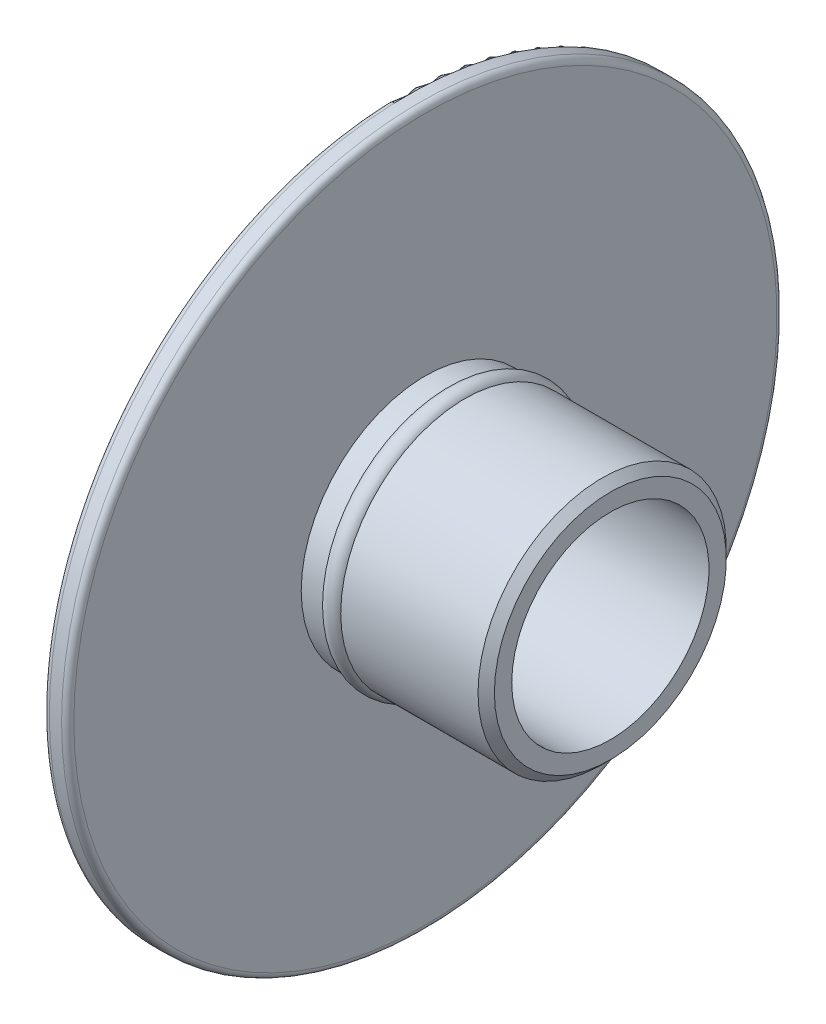
SolidWorks part; units mm, degrees
material "3D Printed PLA"
ref_plane "Front Plane" through (0, 0, 0) normal (0, 0, 1) x (1, 0, 0)
ref_plane "Top Plane" through (0, 0, 0) normal (0, 1, 0) x (1, 0, 0)
ref_plane "Right Plane" through (0, 0, 0) normal (1, 0, 0) x (0, 0, -1)
ref_axis "Axis1" through (0, 55, 0) along (0, -1, 0)
ref_axis "Axis2" through (-88.99, 0, 0) along (1, 0, 0)
ref_axis "Axis3" through (0, 0, -88.99) along (0, 0, 1)
sketch "Sketch1" plane through (0, 0, 0) normal (0, 0, 1) x (1, 0, 0)
  line L0 (0, 0) -> (0, 6029.5309) construction
  line L1 (0, 0) -> (6029.5309, 0) construction
  line L2 (-5.25, 16) -> (-5.25, 17.5)
  line L3 (-5.25, 16) -> (5.25, 16)
  line L4 (-5.25, 16) -> (-5.25, -16)
  line L5 (-5.25, -16) -> (5.25, -16)
  line L6 (5.25, 16) -> (5.25, -16)
  line L7 (-5.25, 17.5) -> (-6.45, 17.5)
  line L8 (-6.45, 17.5) -> (-6.45, -17.5)
  line L9 (-6.45, -17.5) -> (-5.25, -17.5)
  line L10 (-5.25, -17.5) -> (-5.25, -16)
  line L11 (5.25, -17.5) -> (5.25, -16)
  line L12 (6.45, -17.5) -> (5.25, -17.5)
  line L13 (6.45, 17.5) -> (6.45, -17.5)
  line L14 (5.25, 17.5) -> (6.45, 17.5)
  line L15 (5.25, 16) -> (5.25, 17.5)
  line L16 (-6.45, 4.8246) -> (6.45, 4.8246)
  line L17 (-5.05, 7.5246) -> (-5.05, 6.2746)
  line L18 (-5.25, 6.0746) -> (-4.183, 6.0746)
  line L19 (3.8, 6.0746) -> (3.8, 4.8246)
  line L20 (4, 4.8246) -> (4, 6.2746)
  line L21 (4, 6.2746) -> (-3.3929, 6.2746)
  line L22 (-4.1071, 6.2746) -> (-5.05, 6.2746)
  line L23 (-3.3929, 6.2746) -> (-4.1071, 6.2746) construction
  line L24 (-4.183, 6.0746) -> (-3.317, 6.0746) construction
  line L25 (-3.317, 6.0746) -> (3.8, 6.0746)
  line L26 (-5.05, 7.5246) -> (5.25, 7.5246)
  line L27 (-3.75, 5.9246) -> (-3.75, 5.8246) construction
  line L28 (3.8, 6.0746) -> (3.8, 6.2746) construction
  line L29 (3.8, 6.0746) -> (4, 6.0746) construction
  line L30 (-4, -4.8246) -> (-4, -6.2746)
  line L31 (-3.75, 6.3246) -> (-3.75, 6.4246) construction
  line L32 (4, 6.2746) -> (5.25, 6.2746) construction
  line L33 (-5.05, 7.5246) -> (-5.25, 7.5246) construction
  line L34 (-4, -6.2746) -> (3.3929, -6.2746)
  line L35 (4.1071, -6.2746) -> (5.05, -6.2746)
  line L36 (5.05, -7.5246) -> (5.05, -6.2746)
  line L37 (5.05, -7.5246) -> (-5.25, -7.5246)
  line L38 (5.25, -6.0746) -> (4.183, -6.0746)
  line L39 (3.317, -6.0746) -> (-3.8, -6.0746)
  line L40 (-3.8, -6.0746) -> (-3.8, -4.8246)
  line L41 (6.45, -4.8246) -> (-6.45, -4.8246)
  arc A0 (-4.183, 6.0746) -> (-3.317, 6.0746) centre (-3.75, 5.8246) cw
  arc A1 (-4.1071, 6.2746) -> (-3.3929, 6.2746) centre (-3.75, 5.9246) cw
  arc A2 (4.1071, -6.2746) -> (3.3929, -6.2746) centre (3.75, -5.9246) cw
  arc A3 (4.183, -6.0746) -> (3.317, -6.0746) centre (3.75, -5.8246) cw
  point P37 (-3.75, 6.3246)
  point P55 (0, 0)
  point P58 (0, 0)
  dimension "D1" = 0.2
  dimension "D10" = 0.5
  dimension "D2" = 35
  dimension "D3" = 1.2
  dimension "D4" = 10.5
  dimension "D5" = 32
  dimension "D6" = 9.6491
  dimension "D7" = 1.25
  dimension "D8" = 0.25
  dimension "D9" = 0.1
  dimension "D11" = 1.5
  dimension "D12" = 2
sketch "Sketch2" plane through (0, 0, 0) normal (0, 0, 1) x (1, 0, 0)
  line L0 (-6.45, 4.8246) -> (6.45, 4.8246) construction
  line L1 (-6.45, 17.5) -> (-5.25, 17.5)
  line L2 (-6.45, 17.5) -> (-6.45, 4.8246)
  line L3 (-6.45, 4.8246) -> (-5.25, 4.8246)
  line L4 (-5.25, 17.5) -> (-5.25, 4.8246)
  line L5 (-5.25, 16) -> (-5.25, -16) construction
revolve "Revolve1" add sketch "Sketch2" angle 360 about L1
sketch "Sketch4" plane through (0, 0, 0) normal (0, 0, 1) x (1, 0, 0)
  line L0 (-5.25, 6.0746) -> (-5.25, 4.8246)
  line L1 (-5.25, 16) -> (-5.25, -16) construction
  line L2 (-6.45, 4.8246) -> (6.45, 4.8246) construction
  line L3 (-5.25, 4.8246) -> (3.8, 4.8246)
  line L4 (3.8, 4.8246) -> (3.8, 6.0746)
  line L5 (3.8, 6.0746) -> (-3.317, 6.0746)
  line L6 (-5.25, 6.0746) -> (-4.183, 6.0746)
  arc A0 (-3.317, 6.0746) -> (-4.183, 6.0746) centre (-3.75, 5.8246) ccw construction
  arc A1 (-3.317, 6.0746) -> (-4.183, 6.0746) centre (-3.75, 5.8246) ccw
revolve "Revolve2" add sketch "Sketch4" angle 360 about L1
sketch "Sketch5" [suppressed] plane through (0, 0, 0) normal (0, 0, 1) x (1, 0, 0)
  line L0 (-5.25, -4.8246) -> (-4, -4.8246)
  line L1 (6.45, -4.8246) -> (-6.45, -4.8246) construction
  line L2 (-5.25, 16) -> (-5.25, -16) construction
  line L3 (-4, -4.8246) -> (-4, -6.2746)
  line L4 (-4, -6.2746) -> (3.3929, -6.2746)
  line L6 (4.1071, -6.2746) -> (5.05, -6.2746)
  line L7 (5.05, -6.2746) -> (5.05, -7.5246)
  line L8 (5.05, -7.5246) -> (-5.25, -7.5246)
  line L9 (-5.25, -7.5246) -> (-5.25, -4.8246)
  arc A0 (3.3929, -6.2746) -> (4.1071, -6.2746) centre (3.75, -5.9246) ccw construction
  arc A1 (3.3929, -6.2746) -> (4.1071, -6.2746) centre (3.75, -5.9246) ccw
revolve "Revolve3" [suppressed] add sketch "Sketch5" angle 360 about L1
chamfer "Chamfer1" [suppressed] distance 0.4 angle 45
chamfer "Chamfer2" distance 0.4 angle 45 1 edges at (3.8, 0, 6.0746)
fillet "Fillet1" radius 0.3 2 edges at (-5.25, 0, 17.5) (-6.45, 0, 17.5)
sketch "Sketch3" plane through (-6.45, 0, 0) normal (-1, 0, 0) x (0, 0, 1)
  line L0 (0, 17.5) -> (0, -17.5) construction
  line L1 (0, 15.0123) -> (0, 10.0123) construction
  line L2 (0.875, 15.0123) -> (0.875, 10.0123)
  line L3 (-0.875, 15.0123) -> (-0.875, 10.0123)
  line L4 (0, 9.1373) -> (0, 7.5246) construction
  line L5 (0, 17.5) -> (0, 15.8873) construction
  line L6 (0.375, 6.7642) -> (0.375, 5.5619)
  line L7 (0, 0) -> (2.1333, 5.1502) construction
  line L8 (4.5178, 5.0482) -> (3.6677, 4.198)
  line L9 (5.0482, 4.5178) -> (4.198, 3.6677)
  line L10 (6.7642, 0.375) -> (5.5619, 0.375)
  line L11 (6.7642, -0.375) -> (5.5619, -0.375)
  line L12 (5.0482, -4.5178) -> (4.198, -3.6677)
  line L13 (4.5178, -5.0482) -> (3.6677, -4.198)
  line L14 (0.375, -6.7642) -> (0.375, -5.5619)
  line L15 (-0.375, -6.7642) -> (-0.375, -5.5619)
  line L16 (-4.5178, -5.0482) -> (-3.6677, -4.198)
  line L17 (-5.0482, -4.5178) -> (-4.198, -3.6677)
  line L18 (-6.7642, -0.375) -> (-5.5619, -0.375)
  line L19 (-6.7642, 0.375) -> (-5.5619, 0.375)
  line L20 (-5.0482, 4.5178) -> (-4.198, 3.6677)
  line L21 (-4.5178, 5.0482) -> (-3.6677, 4.198)
  line L22 (-0.375, 6.7642) -> (-0.375, 5.5619)
  circle A0 centre (0, 0) radius 7.5246 construction
  circle A1 centre (0, 0) radius 17.5 construction
  arc A2 (0.875, 15.0123) -> (-0.875, 15.0123) centre (0, 15.0123) ccw
  arc A3 (-0.875, 10.0123) -> (0.875, 10.0123) centre (0, 10.0123) ccw
  circle A4 centre (0, 0) radius 4.8246 construction
  arc A5 (3.6677, 4.198) -> (0.375, 5.5619) centre (0, 0) ccw
  arc A6 (4.5178, 5.0482) -> (0.375, 6.7642) centre (0, 0) ccw
  circle A7 centre (0, 0) radius 5.5746 construction
  circle A8 centre (0, 0) radius 6.7746 construction
  arc A9 (6.7642, 0.375) -> (5.0482, 4.5178) centre (0, 0) ccw
  arc A10 (5.5619, 0.375) -> (4.198, 3.6677) centre (0, 0) ccw
  arc A11 (5.0482, -4.5178) -> (6.7642, -0.375) centre (0, 0) ccw
  arc A12 (4.198, -3.6677) -> (5.5619, -0.375) centre (0, 0) ccw
  arc A13 (0.375, -6.7642) -> (4.5178, -5.0482) centre (0, 0) ccw
  arc A14 (0.375, -5.5619) -> (3.6677, -4.198) centre (0, 0) ccw
  arc A15 (-4.5178, -5.0482) -> (-0.375, -6.7642) centre (0, 0) ccw
  arc A16 (-3.6677, -4.198) -> (-0.375, -5.5619) centre (0, 0) ccw
  arc A17 (-6.7642, -0.375) -> (-5.0482, -4.5178) centre (0, 0) ccw
  arc A18 (-5.5619, -0.375) -> (-4.198, -3.6677) centre (0, 0) ccw
  arc A19 (-5.0482, 4.5178) -> (-6.7642, 0.375) centre (0, 0) ccw
  arc A20 (-4.198, 3.6677) -> (-5.5619, 0.375) centre (0, 0) ccw
  arc A21 (-0.375, 6.7642) -> (-4.5178, 5.0482) centre (0, 0) ccw
  arc A22 (-0.375, 5.5619) -> (-3.6677, 4.198) centre (0, 0) ccw
  point P10 (0, 12.5123)
  point P60 (0, 0)
  dimension "D1" = 6.75
  dimension "D3" = 0.75
  dimension "D4" = 0.75
  dimension "D2" = 1.75
  dimension "D5" = 0.75
  dimension "D6" = 22.5
  dimension "D7" = 8
extrude "Cut-Extrude2" cut sketch "Sketch3<3>" against normal blind 0.6 contours L8 A6 L6 A5 | A10 L10 A9 L9 | A14 L14 A13 L13 | A16 L16 A15 L15 | A18 L18 A17 L17 | A20 L20 A19 L19 | A22 L22 A21 L21 | A12 L12 A11 L11 region at (-6.45, 5.6211, 2.3283) region at (-6.45, 2.3283, 5.6211) region at (-6.45, -2.3283, 5.6211) region at (-6.45, -5.6211, 2.3283) region at (-6.45, -5.6211, -2.3283) region at (-6.45, -2.3283, -5.6211) region at (-6.45, 2.3283, -5.6211) region at (-6.45, 5.6211, -2.3283)
sketch "Sketch3<3>" plane through (-6.45, 0, 0) normal (-1, 0, 0) x (0, 0, 1) same geometry as "Sketch3"
fillet "Fillet2" radius 0.3 32 edges at (-6.15, 0.375, 5.5619) (-6.15, 0.375, 6.7642) (-6.15, 4.5178, 5.0482) (-6.15, 3.6677, 4.198) (-6.15, -0.375, -5.5619) (-6.15, -0.375, -6.7642) (-6.15, -4.5178, -5.0482) (-6.15, -3.6677, -4.198) (-6.15, 5.5619, -0.375) (-6.15, 6.7642, -0.375) (-6.15, 5.0482, -4.5178) (-6.15, 4.198, -3.6677) (-6.15, -3.6677, 4.198) (-6.15, -4.5178, 5.0482) (-6.15, -0.375, 6.7642) (-6.15, -0.375, 5.5619) (-6.15, 5.0482, 4.5178) (-6.15, 5.5619, 0.375) (-6.15, 4.198, 3.6677) (-6.15, 3.6677, -4.198) (-6.15, 4.5178, -5.0482) (-6.15, 0.375, -6.7642) (-6.15, 0.375, -5.5619) (-6.15, -4.198, -3.6677) (-6.15, -5.0482, -4.5178) (-6.15, -6.7642, -0.375) (-6.15, -5.5619, -0.375) (-6.15, -5.5619, 0.375) (-6.15, -6.7642, 0.375) (-6.15, -5.0482, 4.5178) (-6.15, -4.198, 3.6677) (-6.15, 6.7642, 0.375)
extrude "Single-Slot" [suppressed] cut sketch "Sketch3" against normal up to next contours L3 A3 L2 A2
mirror "Double-Slot" [suppressed] about plane through (0, 0, 0) normal (0, 1, 0)
